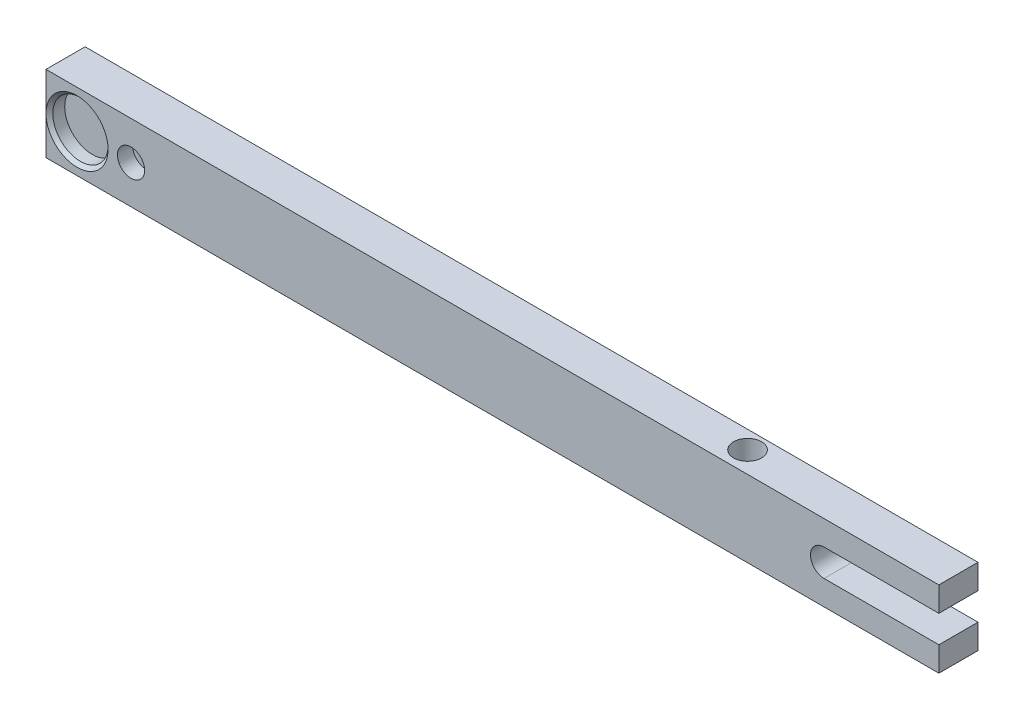
SolidWorks part; units mm, degrees
ref_plane "Front" through (0, 0, 0) normal (0, 0, 1) x (1, 0, 0)
ref_plane "Top" through (0, 0, 0) normal (0, 1, 0) x (1, 0, 0)
ref_plane "Right" through (0, 0, 0) normal (1, 0, 0) x (0, 0, -1)
sketch "Sketch1" plane through (0, 0, 0) normal (0, 0, 1) x (1, 0, 0)
  line L1 (52.5, -4.5) -> (-52.5, -4.5)
  line L2 (52.5, -4.5) -> (52.5, 4.5)
  line L3 (52.5, 4.5) -> (-52.5, 4.5)
  line L4 (-52.5, -4.5) -> (-52.5, 4.5)
  line L5 (52.5, -4.5) -> (-52.5, 4.5) construction
  line L6 (52.5, 4.5) -> (-52.5, -4.5) construction
  point P0 (0, 0)
  dimension "D1" = 9
  dimension "D2" = 105
extrude "Boss-Extrude1" add sketch "Sketch1" along normal blind 5
sketch "Sketch2" plane through (0, 4.5, 0) normal (0, 1, 0) x (1, 0, 0)
  line L0 (52.5, -5) -> (52.5, 0) construction
  line L2 (52.5, 0) -> (-52.5, 0) construction
  circle A0 centre (27.5, -2.5) radius 1.65
  dimension "D3" = 3.3
  dimension "D2" = 25
  dimension "D1" = 2.5
sketch "Sketch4" plane through (0, 0, 5) normal (0, 0, 1) x (1, 0, 0)
  line L0 (39, 0) -> (45, 0) construction
  line L1 (39, 1.6) -> (45, 1.6)
  line L2 (39, -1.6) -> (45, -1.6)
  arc A0 (39, 1.6) -> (39, -1.6) centre (39, 0) ccw
  arc A1 (45, -1.6) -> (45, 1.6) centre (45, 0) ccw
  point P2 (42, 0)
  dimension "D1" = 1.6
  dimension "D2" = 42
  dimension "D3" = 6
extrude "Cut-Extrude1" cut sketch "Sketch4" against normal blind 5
sketch "Sketch8" plane through (0, 0, 5) normal (0, 0, 1) x (1, 0, 0)
  line L0 (45, 1.6) -> (39, 1.6) construction
  line L1 (44.5, 1.6) -> (52.5, 1.6)
  line L2 (44.5, 1.6) -> (44.5, -1.6)
  line L3 (44.5, -1.6) -> (52.5, -1.6)
  line L4 (52.5, 1.6) -> (52.5, -1.6)
  line L5 (52.5, -4.5) -> (52.5, 4.5) construction
  line L6 (39, -1.6) -> (45, -1.6) construction
  dimension "D1" = 8
extrude "Cut-Extrude4" cut sketch "Sketch8" against normal blind 10
ref_plane "Plane1" through (-48.5, 0, 0) normal (-1, 0, 0) x (0, 0, 1)
sketch "Sketch7" plane through (0, 0, 5) normal (0, 0, -1) x (-1, 0, 0)
  line L0 (52.5, 4.5) -> (52.5, -4.5) construction
  line L1 (52.5, 4.5) -> (52.5, -4.5) construction
  circle A0 centre (48.85, 0) radius 3.25
  circle A1 centre (42.5, 0) radius 1.6
  dimension "D1" = 6.5
  dimension "D3" = 10
  dimension "D2" = 3.65
extrude "Cut-Extrude2" cut sketch "Sketch7" along normal blind 1.8
chamfer "Chamfer1" distance 0.4 angle 45 1 edges at (-52.1, 0, 5)
chamfer "Chamfer2" distance 0.4 angle 45 8 edges at (52.5, 3.05, 0) (52.5, -3.05, 0) (0, 4.5, 0) (-52.5, 0, 0) (0, -4.5, 0) (45.75, -1.6, 0) (37.4, 0, 0) (45.75, 1.6, 0)
extrude "Cut-Extrude3" cut sketch "Sketch2" against normal blind 10
sketch "Sketch10" plane through (0, 0, 0) normal (0, 0, 1) x (1, 0, 0)
  line L2 (29.15, -4.5) -> (29.15, 4.5) construction
  circle A0 centre (-2.5, 0) radius 1.5
  dimension "D1" = 3
  dimension "D2" = 31.65
extrude "Cut-Extrude5" cut sketch "Sketch10" against normal mid plane 8 contours A0
